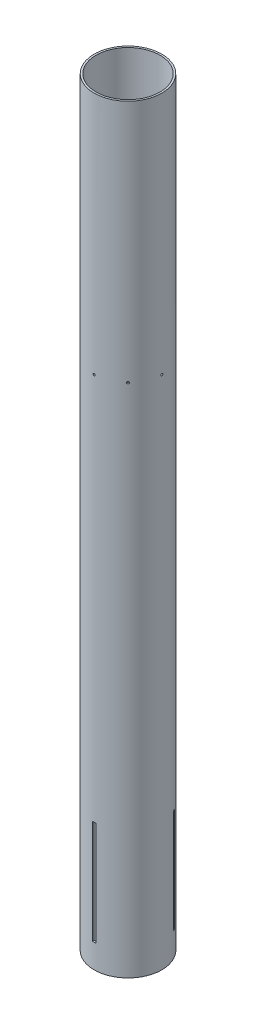
SolidWorks part; units mm, degrees
material "Hexcel AS4C (3000 Filaments)"
ref_plane "Front Plane" through (0, 0, 0) normal (0, 0, 1) x (1, 0, 0)
ref_plane "Top Plane" through (0, 0, 0) normal (0, 1, 0) x (1, 0, 0)
ref_plane "Right Plane" through (0, 0, 0) normal (1, 0, 0) x (0, 0, -1)
sketch "Sketch1" plane through (0, 0, 0) normal (0, 1, 0) x (1, 0, 0)
  circle A0 centre (0, 0) radius 50.8
  dimension "D1" = 101.6
extrude "Body Tube Extrusion" add sketch "Sketch1" along normal blind 1206.5 thin thin type one direction wall 2.921
ref_plane "Plane1" through (0, 0, 53.721) normal (0, 0, 1) x (1, 0, 0)
sketch "Sketch2" plane through (0, 0, 53.721) normal (0, 0, 1) x (1, 0, 0)
  line L0 (0, 1206.5) -> (0, 0) construction
  line L1 (50.8, 1206.5) -> (-50.8, 1206.5) construction
  line L2 (-53.721, 0) -> (53.721, 0) construction
  circle A0 centre (0, 819.15) radius 1.6383
  dimension "D1" = 3.2766
  dimension "D2" = 819.15
extrude "Engine Block Hole" cut sketch "Sketch2" against normal up to next
pattern_circular "CirPattern1" count 8 over 360 about axis through (0, 1206.5, 0) along (0, -1, 0) of "Engine Block Hole"
sketch "Sketch3" plane through (0, 0, 53.721) normal (0, 0, 1) x (1, 0, 0)
  line L0 (0, 0) -> (0, 38.1) construction
  line L1 (-50.8, 0) -> (50.8, 0) construction
  line L2 (0, 1206.5) -> (0, 0) construction
  line L4 (-2.667, 203.2) -> (2.667, 203.2)
  line L5 (-2.667, 203.2) -> (-2.667, 38.1)
  line L6 (-2.667, 38.1) -> (2.667, 38.1)
  line L7 (2.667, 203.2) -> (2.667, 38.1)
  point P10 (0, 38.1)
  dimension "D1" = 165.1
  dimension "D2" = 5.334
  dimension "D3" = 38.1
extrude "Fin Tab Slots" cut sketch "Sketch3" against normal blind 2.54
pattern_circular "CirPattern2" count 3 over 360 about axis through (0, 1206.5, 0) along (0, -1, 0) of "Fin Tab Slots" reverse direction yes
